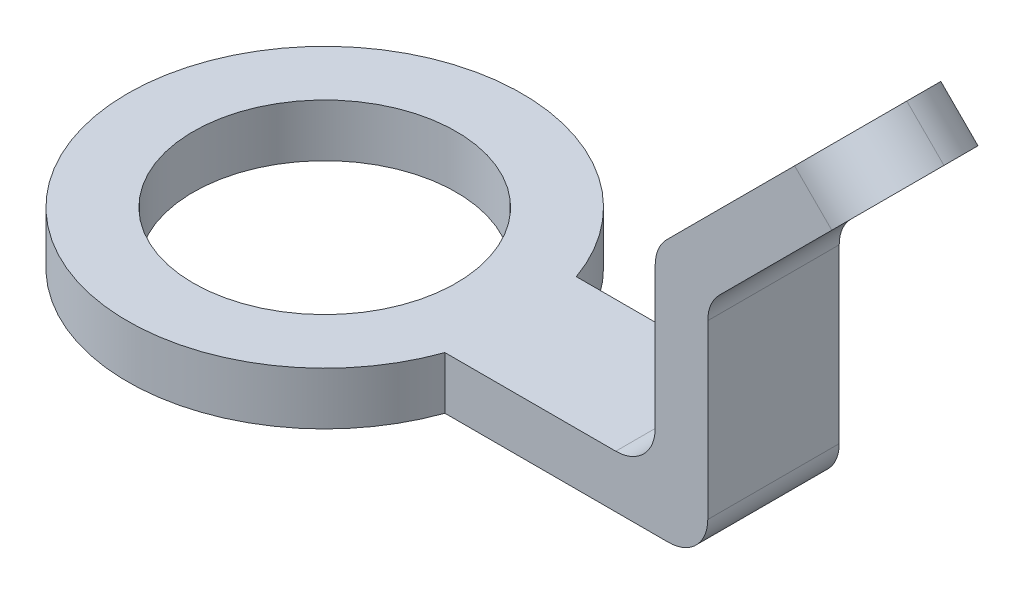
SolidWorks part; units mm, degrees
ref_plane "Front Plane" through (0, 0, 0) normal (0, 0, 1) x (1, 0, 0)
ref_plane "Top Plane" through (0, 0, 0) normal (0, 1, 0) x (1, 0, 0)
ref_plane "Right Plane" through (0, 0, 0) normal (1, 0, 0) x (0, 0, -1)
sketch "Sketch2" plane through (0, 0, 0) normal (0, 1, 0) x (1, 0, 0)
  line L0 (0, 0) -> (34.1421, 0) construction
  line L1 (34.1421, 5) -> (34.1421, -5)
  line L2 (34.1421, -5) -> (14.1421, -5)
  line L3 (34.1421, 5) -> (14.1421, 5)
  arc A0 (14.1421, 5) -> (14.1421, -5) centre (0, 0) ccw
  circle A1 centre (0, 0) radius 10
  dimension "D1" = 30
  dimension "D5" = 20
  dimension "D2" = 5
  dimension "D3" = 5
  dimension "D4" = 20
extrude "Boss-Extrude1" add sketch "Sketch2" along normal blind 4
sketch "Sketch3" plane through (0, 0, 5) normal (0, 0, 1) x (1, 0, 0)
  line L0 (34.1421, 4) -> (34.1421, 17.3431)
  line L1 (34.1421, 17.3431) -> (47.1127, 30.3137)
  line L2 (47.1127, 30.3137) -> (44.2843, 33.1421)
  line L3 (44.2843, 33.1421) -> (30.1421, 19)
  line L4 (30.1421, 19) -> (30.1421, 4)
  line L5 (14.1421, 4) -> (34.1421, 4) construction
  line L6 (30.1421, 4) -> (34.1421, 4)
  dimension "D1" = 4
  dimension "D2" = 4
  dimension "D3" = 135
  dimension "D4" = 15
  dimension "D5" = 20
extrude "Boss-Extrude2" add sketch "Sketch3" against normal blind 10
sketch "Sketch4" plane through (0, 0, 0) normal (0, -1, 0) x (1, 0, 0)
  circle A0 centre (0, 0) radius 12
  circle A1 centre (0, 0) radius 13
  dimension "D1" = 24
  dimension "D2" = 26
extrude "Boss-Extrude3" add sketch "Sketch4" along normal blind 1
fillet "Fillet1" radius 5 2 edges at (45.6985, 31.7279, -5) (45.6985, 31.7279, 5)
sketch "Sketch5" plane through (5.5711, -5.5711, 0) normal (-0.7071, 0.7071, 0) x (0.7071, 0.7071, 0)
  circle A0 centre (49.7487, 0) radius 2.5
  dimension "D1" = 5
hole_wizard "M3 Clearance Hole1" positions "Sketch6" profile "Sketch7" hole size "M3" standard "ANSI Metric" end condition through all
sketch "Sketch6" plane through (5.5711, -5.5711, 0) normal (-0.7071, 0.7071, 0) x (0.7071, 0.7071, 0)
  point P0 (49.7487, 0)
sketch "Sketch7" plane through (40.7487, 29.6066, 0) normal (0, 0, 1) x (-0.7071, -0.7071, 0)
  line L0 (0, 0) -> (0, 26.1421)
  line L1 (0, 26.1421) -> (1.8, 26.1421)
  line L2 (1.8, 26.1421) -> (1.8, 0)
  line L5 (1.8, 0) -> (0, 0)
  line L11 (0, -6.35) -> (0, 107.95) construction
  dimension "Thru Hole Dia." = 3.6
  dimension "Thru Hole Depth" = 26.1421
fillet "Fillet2" radius 3 4 edges at (34.1421, 17.3431, 0) (30.1421, 19, 0) (34.1421, 0, 0) (30.1421, 4, 0)
